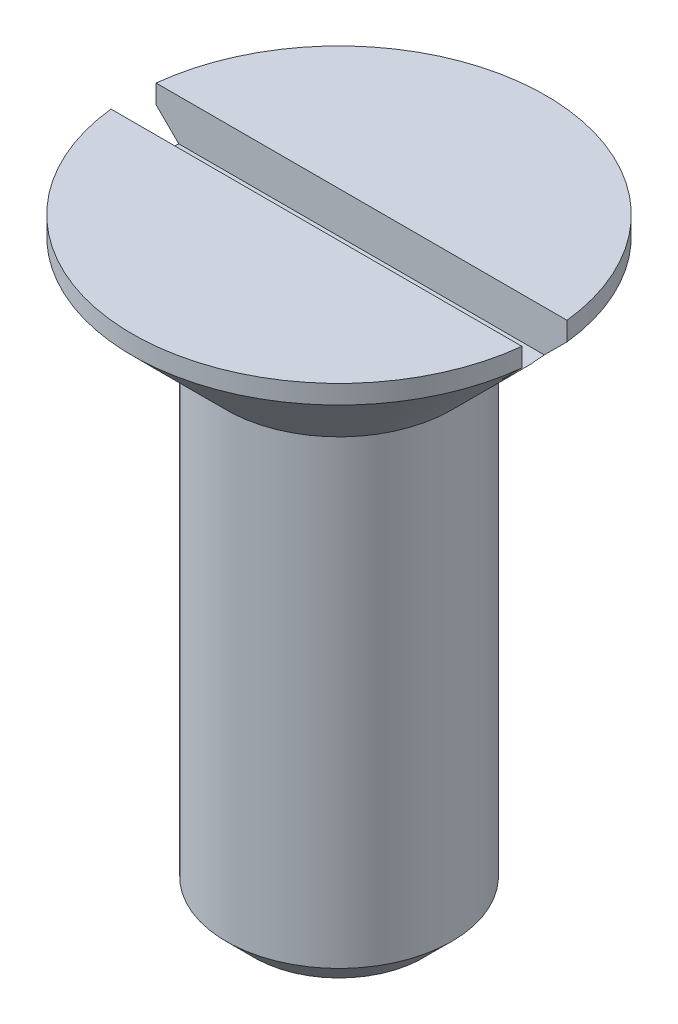
SolidWorks part; units mm, degrees
ref_plane "Спереди" through (0, 0, 0) normal (0, 0, 1) x (1, 0, 0)
ref_plane "Сверху" through (0, 0, 0) normal (0, 1, 0) x (1, 0, 0)
ref_plane "Справа" through (0, 0, 0) normal (1, 0, 0) x (0, 0, -1)
sketch "Эскиз1" plane through (0, 0, 0) normal (0, 0, 1) x (1, 0, 0)
  line L0 (0, 125.7632) -> (0, 0) construction
  line L2 (0, 16) -> (0, 0)
  line L3 (0, 16) -> (5.5, 16)
  line L4 (3, 13) -> (3, 0)
  line L5 (3, 13) -> (5.5, 15.5)
  line L6 (3, 0) -> (0, 0)
  line L7 (5.5, 16) -> (5.5, 15.5)
  dimension "D1" = 5.5
  dimension "D2" = 16
  dimension "D3" = 3
  dimension "D4" = 45
  dimension "D5" = 3
revolve "Повернуть1" add sketch "Эскиз1" angle 360 about L0
ref_axis "Ось4" through (0, 18.7854, 0) along (0, -1, 0)
sketch "Эскиз13" plane through (0, 16, 0) normal (0, 1, 0) x (-1, 0, 0)
  line L1 (6, -0.6) -> (-6, -0.6)
  line L2 (6, -0.6) -> (6, 0.6)
  line L3 (6, 0.6) -> (-6, 0.6)
  line L4 (-6, -0.6) -> (-6, 0.6)
  dimension "D1" = 6
  dimension "D2" = 12
  dimension "D3" = 0.6
  dimension "D4" = 1.2
extrude "Вырез-Вытянуть9" cut sketch "Эскиз13" against normal blind 1.1
chamfer "Фаска1" distance 0.75 angle 45 1 edges at (-3, 0, 0)
